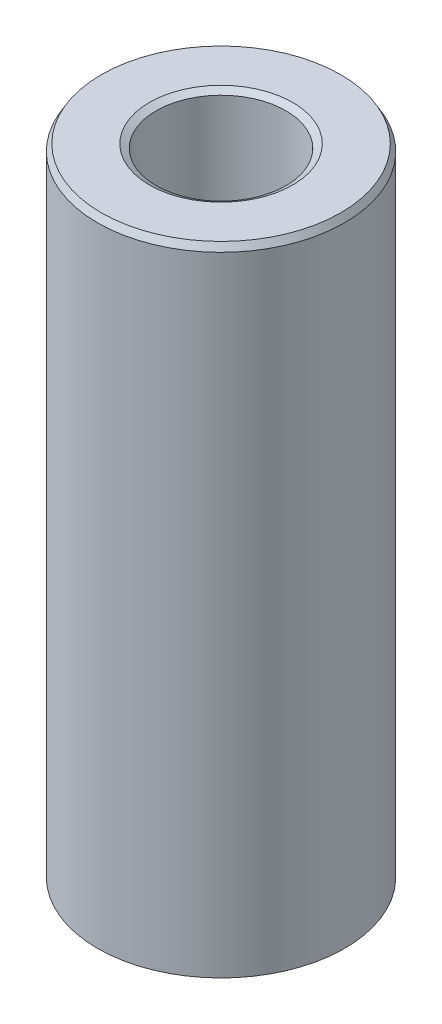
SolidWorks part; units mm, degrees
ref_plane "Front Plane" through (0, 0, 0) normal (0, 0, 1) x (1, 0, 0)
ref_plane "Top Plane" through (0, 0, 0) normal (0, 1, 0) x (1, 0, 0)
ref_plane "Right Plane" through (0, 0, 0) normal (1, 0, 0) x (0, 0, -1)
sketch "Sketch1" plane through (0, 0, 0) normal (0, 1, 0) x (1, 0, 0)
  circle A0 centre (0, 0) radius 52.5
  dimension "SLEEVE_OD" = 105
extrude "Boss-Extrude1" add sketch "Sketch1" along normal blind 271.5125
sketch "Sketch2" plane through (0, 0, 0) normal (0, 1, 0) x (1, 0, 0)
  circle A0 centre (0, 0) radius 27.5813
  dimension "BORE_D" = 55.1627
extrude "Cut-Extrude1" cut sketch "Sketch2" along normal through all
chamfer "Chamfer1" distance 2.8491 angle 30 4 edges at (0, 271.5125, 27.5813) (0, 0, 27.5813) (0, 0, 52.5) (0, 271.5125, 52.5) first distance on face at (0, 271.5125, 27.5813) first distance on face at (0, 0, 27.5813) first distance on face at (0, 271.5125, 52.5)
